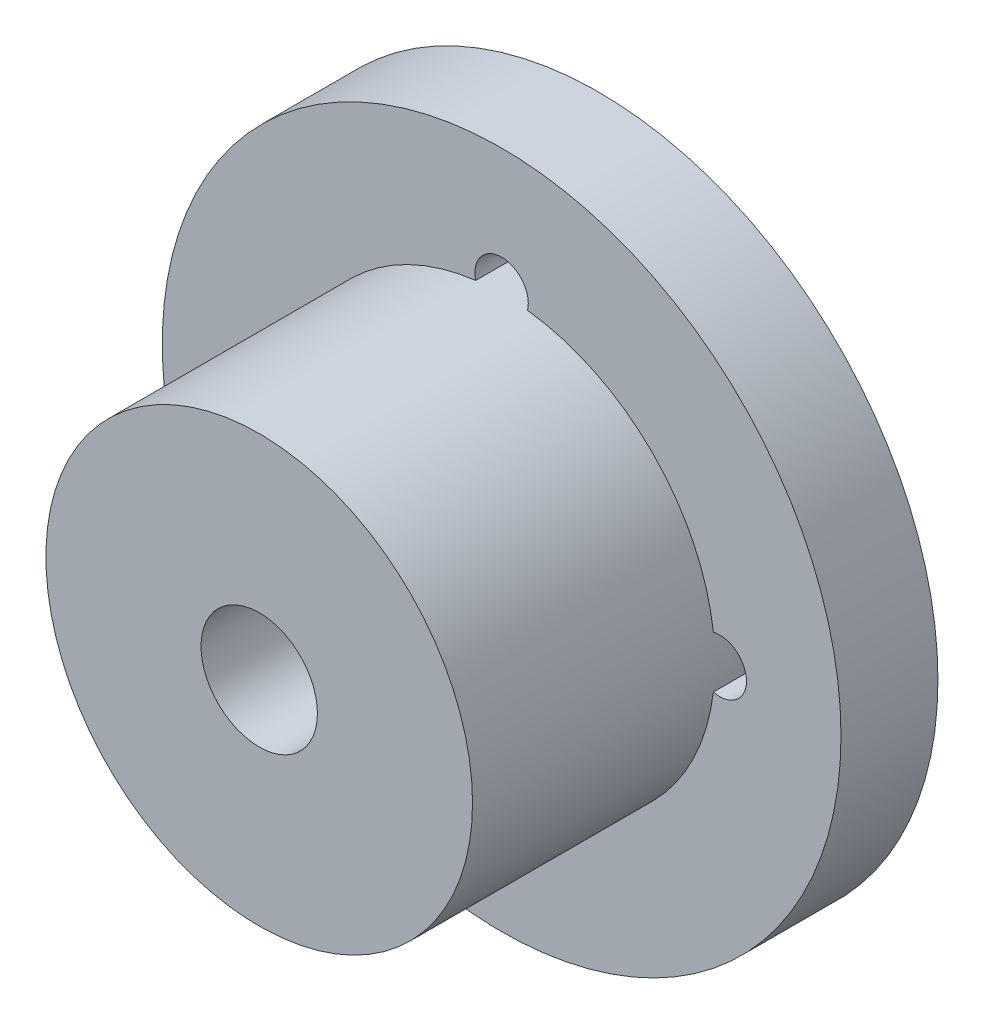
SolidWorks part; units mm, degrees
ref_plane "Front Plane" through (0, 0, 0) normal (0, 0, 1) x (1, 0, 0)
ref_plane "Top Plane" through (0, 0, 0) normal (0, 1, 0) x (1, 0, 0)
ref_plane "Right Plane" through (0, 0, 0) normal (1, 0, 0) x (0, 0, -1)
sketch "Sketch1" plane through (0, 0, 0) normal (0, 0, 1) x (1, 0, 0)
  circle A0 centre (0, 0) radius 35
  circle A1 centre (0, 0) radius 6
  circle A2 centre (22.5, 0) radius 2.75
  circle A3 centre (0, 22.5) radius 2.75
  circle A4 centre (-22.5, 0) radius 2.75
  circle A5 centre (0, -22.5) radius 2.75
extrude "Boss-Extrude1" add sketch "Sketch1" along normal blind 10
sketch "Sketch2" plane through (0, 0, 0) normal (0, 0, 1) x (1, 0, 0)
  circle A0 centre (0, 0) radius 22
  circle A1 centre (0, 0) radius 6
extrude "Boss-Extrude2" add sketch "Sketch2" along normal blind 35
sketch "Sketch3" plane through (0, 0, 0) normal (0, 0, 1) x (1, 0, 0)
  circle A0 centre (0, 0) radius 12
  circle A1 centre (0, 0) radius 4
extrude "Boss-Extrude3" add sketch "Sketch3" along normal blind 20
ref_axis "Axis1" through (0, 0, -1.75) along (0, 0, 1)
sketch3d "3DSketch1"
  point P0 (0, 0, 0)
